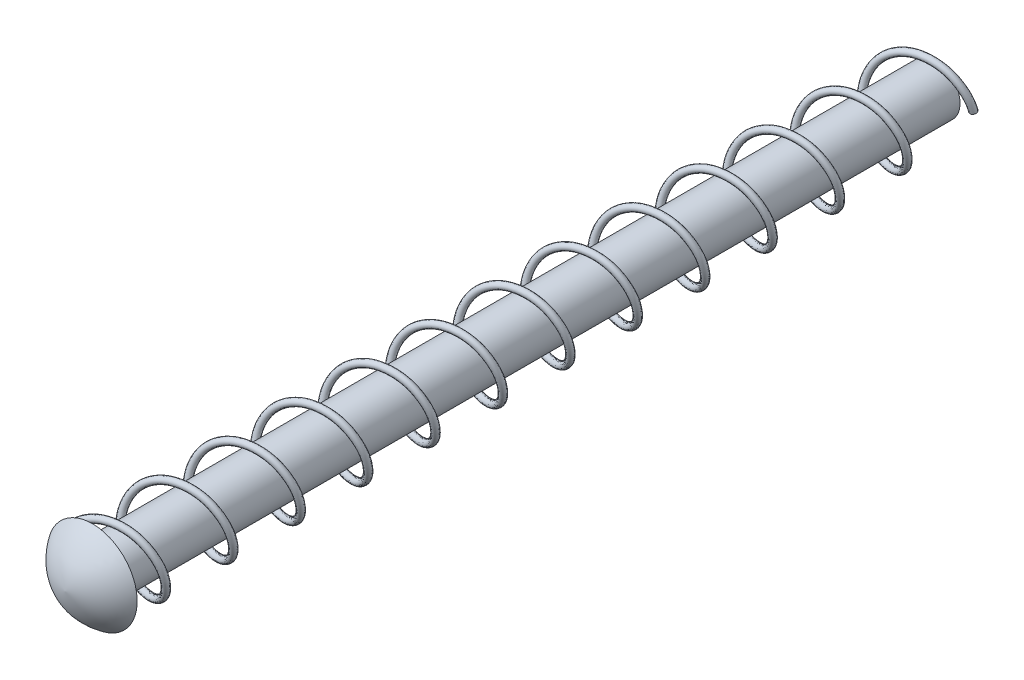
SolidWorks part; units mm, degrees
ref_plane "Front Plane" through (0, 0, 0) normal (0, 0, 1) x (1, 0, 0)
ref_plane "Top Plane" through (0, 0, 0) normal (0, 1, 0) x (1, 0, 0)
ref_plane "Right Plane" through (0, 0, 0) normal (1, 0, 0) x (0, 0, -1)
sketch "Sketch1" plane through (0, 0, 0) normal (0, 0, 1) x (1, 0, 0)
  circle A0 centre (0, 0) radius 0.37
  dimension "D1" = 0.74
extrude "Boss-Extrude1" add sketch "Sketch1" along normal blind 12.5
sketch "Sketch3" plane through (0, 0, 0) normal (1, 0, 0) x (0, 0, -1)
  line L0 (-12.5, 0.6638) -> (-12.5, 0)
  line L1 (-12.5, 0.37) -> (-12.5, -0.37) construction
  line L2 (-12.5, 0) -> (-12.9059, 0)
  arc A3 (-12.5, 0.6638) -> (-12.9059, 0) centre (-12.0049, -0.0949) ccw
revolve "Revolve1" add sketch "Sketch3" angle 360 about L2
sketch "Sketch5" plane through (0, 0, 0) normal (0, 0, -1) x (-1, 0, 0)
  circle A0 centre (0, 0) radius 0.5675
curve "Helix/Spiral1" pitch 1 height 12.5 radius 0.5675 centre (0, 0, 0) axis (0, 0, 1) start towards (1, 0, 0)
sweep "Sweep2" add path "Helix/Spiral1" circular profile diameter 0.1 parameters "D3"=0.1
